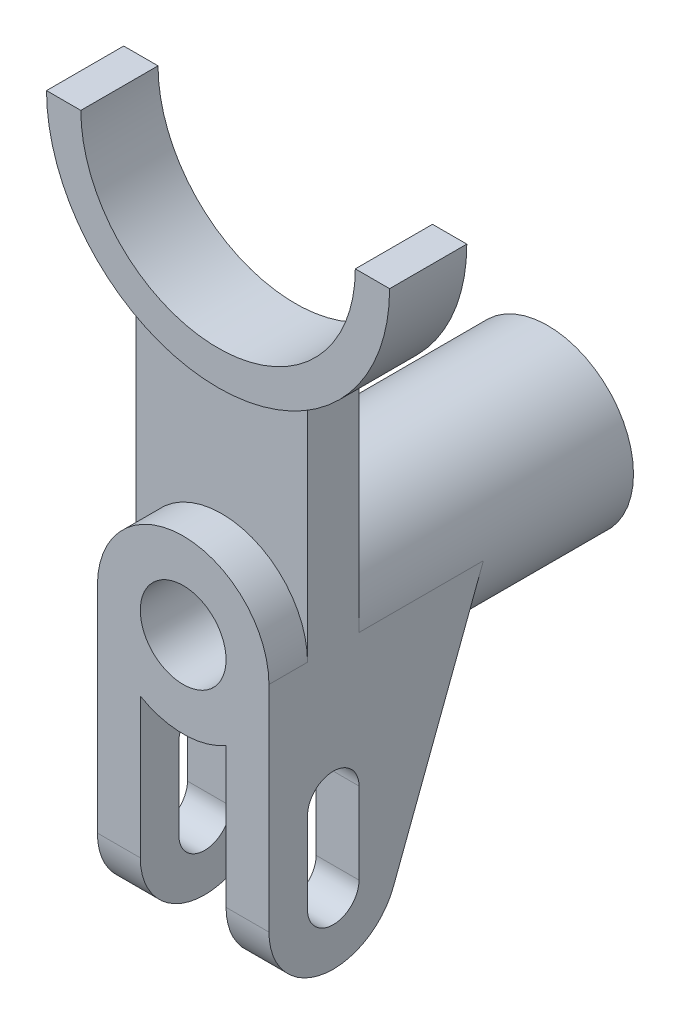
SolidWorks part; units mm, degrees
material "구리"
ref_plane "정면" through (0, 0, 0) normal (0, 0, 1) x (1, 0, 0)
ref_plane "윗면" through (0, 0, 0) normal (0, 1, 0) x (1, 0, 0)
ref_plane "우측면" through (0, 0, 0) normal (1, 0, 0) x (0, 0, -1)
sketch "Sketch1" plane through (0, 0, 0) normal (0, 0, 1) x (1, 0, 0)
  line L0 (-37.8626, 88) -> (-29.8626, 88)
  line L1 (34.1374, 88) -> (42.1374, 88)
  line L2 (-20, 0) -> (-20, 54.6843)
  line L3 (20, 0) -> (20, 52.21)
  circle A0 centre (0, 0) radius 20
  arc A1 (-37.8626, 88) -> (42.1374, 88) centre (2.1374, 88) ccw
  arc A3 (-29.8626, 88) -> (34.1374, 88) centre (2.1374, 88) ccw
  circle A4 centre (2.1374, 88) radius 40 construction
  circle A5 centre (2.1374, 88) radius 32 construction
  dimension "D1" = 40
  dimension "D2" = 80
  dimension "D4" = 88
  dimension "D3" = 8
extrude "Boss-Extrude1" add sketch "Sketch1" along normal mid plane 18 contours A3 L0 A1 L1 region at (-33.8626, 87.1056, 0)
extrude "Boss-Extrude2" add sketch "Sketch1<3>" along normal mid plane 12 contours A1 L2 A0 L3 region at (-0.2276, 32.5062, 0)
sketch "Sketch1<3>" plane through (0, 0, 0) normal (0, 0, 1) x (1, 0, 0) same geometry as "Sketch1"
extrude "Boss-Extrude3" add sketch "Sketch1<4>" along normal blind 15 and the other way blind 70 contours A0 region at (0, 0, 0)
sketch "Sketch1<4>" plane through (0, 0, 0) normal (0, 0, 1) x (1, 0, 0) same geometry as "Sketch1"
sketch "Sketch2" plane through (20, 0, 0) normal (1, 0, 0) x (0, 0, -1)
  line L0 (-15, 0) -> (-15, -50)
  line L1 (-15, 20) -> (-15, -20) construction
  line L2 (14.0257, -55.318) -> (35, 0)
  line L3 (35, 0) -> (-15, 0)
  line L4 (0, -50) -> (0, -31) construction
  line L5 (-6, -50) -> (-6, -31)
  line L6 (6, -50) -> (6, -31)
  line L8 (-9, 88) -> (9, 88) construction
  arc A0 (-15, -50) -> (14.0257, -55.318) centre (0, -50) ccw
  arc A1 (-6, -50) -> (6, -50) centre (0, -50) ccw
  arc A2 (6, -31) -> (-6, -31) centre (0, -31) ccw
  point P6 (0, -40.5)
  dimension "D2" = 15
  dimension "D4" = 6
  dimension "D1" = 50
  dimension "D3" = 19
  dimension "D5" = 153
ref_plane "Plane1" through (0, 0, 0) normal (1, 0, 0) x (0, 0, -1)
extrude "Boss-Extrude4" add sketch "Sketch2" against normal blind 10
mirror "Mirror1" about plane through (0, 0, 0) normal (1, 0, 0) of "Boss-Extrude4"
hole_wizard "Ø20.0 (20) Diameter Hole1" positions "3DSketch1" profile "Sketch3" hole size "Ø20.0" standard "Ansi Metric" end condition up to next
sketch3d "3DSketch1"
  line L0 (0, 0, 6) -> (0, 0, 15) construction
  point P0 (0, 0, 0)
  point P3 (0, 0, 15)
sketch "Sketch3" plane through (0, 0, 15) normal (1, 0, 0) x (0, -1, 0)
  line L0 (0, 0) -> (0, 85.001)
  line L1 (0, 85.001) -> (10, 85.001)
  line L2 (10, 85.001) -> (10, 0)
  line L5 (10, 0) -> (0, 0)
  line L11 (0, -6.35) -> (0, 107.95) construction
  dimension "관통 구멍 지름" = 20
  dimension "관통 구멍 깊이" = 85.001
